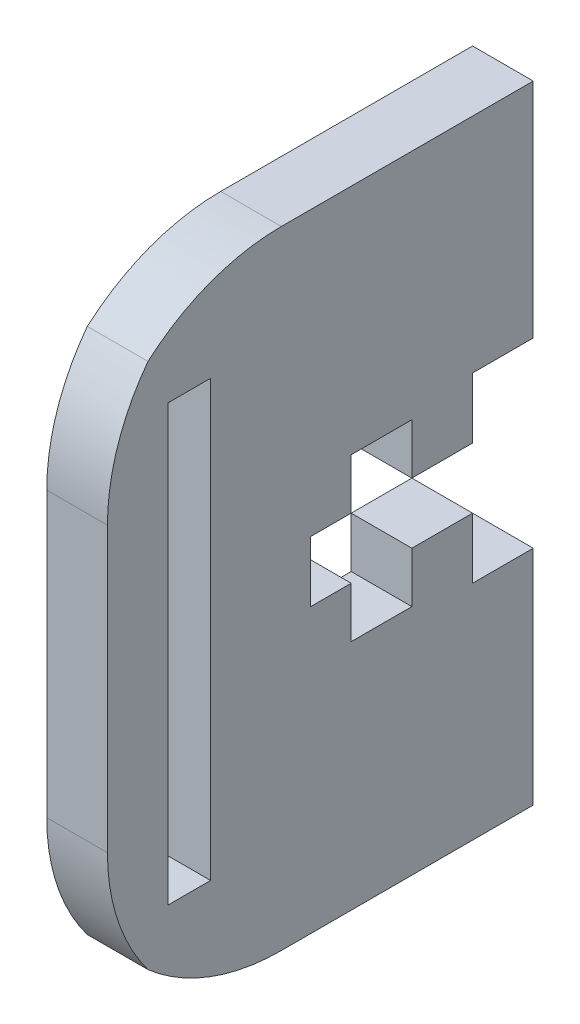
SolidWorks part; units mm, degrees
ref_plane "Alzado" through (0, 0, 0) normal (0, 0, 1) x (1, 0, 0)
ref_plane "Planta" through (0, 0, 0) normal (0, 1, 0) x (1, 0, 0)
ref_plane "Vista lateral" through (0, 0, 0) normal (1, 0, 0) x (0, 0, -1)
sketch "Croquis1" plane through (0, 0, 0) normal (1, 0, 0) x (0, 0, -1)
  line L1 (-10, -12.5) -> (14, -12.5)
  line L2 (-10, -12.5) -> (-10, 12.5)
  line L3 (-10, 12.5) -> (17, 12.5)
  line L5 (-10, -12.5) -> (14, 17.5) construction
  line L6 (-10, 12.5) -> (14, -17.5) construction
  line L8 (14, 4.5) -> (17, 4.5)
  line L10 (14, -4.5) -> (17, -4.5)
  line L12 (14, -4.5) -> (14, 4.5)
  line L13 (-1.05, -10.75) -> (1.05, -10.75)
  line L14 (-1.05, -10.75) -> (-1.05, 10.75)
  line L15 (-1.05, 10.75) -> (1.05, 10.75)
  line L16 (1.05, -10.75) -> (1.05, 10.75)
  line L17 (-1.05, -10.75) -> (1.05, 10.75) construction
  line L18 (-1.05, 10.75) -> (1.05, -10.75) construction
  line L21 (14, 4.5) -> (17, 4.5)
  line L22 (17, 12.5) -> (17, 4.5)
  line L23 (14, -12.5) -> (17, -12.5)
  line L25 (14, -4.5) -> (17, -4.5)
  line L26 (17, -12.5) -> (17, -4.5)
  point P0 (0, 0)
  point P4 (0, 0)
  point P17 (16.9322, 12.5)
  dimension "D1" = 21.5
  dimension "D2" = 25
  dimension "D3" = 2.1
  dimension "D4" = 8
  dimension "D5" = 8
  dimension "D6" = 3
  dimension "D8" = 10
extrude "Saliente-Extruir1" add sketch "Croquis1" along normal mid plane 3 contours L23 L26 L10 L12 L8 L22 L3 L2 L1 L16 L13 L14 L15 region at (0, 0, -3.2247)
fillet "Redondeo1" radius 10 2 edges at (0, -12.5, 10) (0, 12.5, 10)
sketch "Croquis2" plane through (0, 12.5, 0) normal (0, 1, 0) x (1, 0, 0)
  line L4 (-1.5, 17) -> (-1.5, 0)
  line L5 (-1.5, 0) -> (1.5, 0)
  line L6 (-1.5, 17) -> (-1.5, 0)
  line L7 (1.5, 0) -> (1.5, 17)
  line L9 (-1.5, 0) -> (1.5, 0)
  line L12 (1.5, 0) -> (1.5, 17)
  line L13 (1.5, 17) -> (-1.5, 17)
  line L14 (1.5, 17) -> (-1.5, 17)
  dimension "D1" = 0
extrude "Saliente-Extruir2" add sketch "Croquis2" along normal blind 3
sketch "Croquis3" plane through (0, -12.5, 0) normal (0, -1, 0) x (1, 0, 0)
  line L4 (1.5, -17) -> (1.5, 0)
  line L5 (1.5, 0) -> (-1.5, 0)
  line L6 (1.5, -17) -> (1.5, 0)
  line L7 (-1.5, 0) -> (-1.5, -17)
  line L9 (1.5, 0) -> (-1.5, 0)
  line L12 (-1.5, 0) -> (-1.5, -17)
  line L13 (-1.5, -17) -> (1.5, -17)
  line L14 (-1.5, -17) -> (1.5, -17)
  dimension "D1" = 0
extrude "Saliente-Extruir3" add sketch "Croquis3" along normal blind 3
sketch "Croquis4" plane through (-1.5, 0, 0) normal (-1, 0, 0) x (0, 0, 1)
  line L0 (-12, 0) -> (-10.5, 0) construction
  line L1 (-12, 11) -> (-12, -11) construction
  line L2 (-10.5, 11) -> (-10.5, -11) construction
  line L4 (-12.1, -12.4514) -> (-10.4, -12.4514)
  line L5 (-12.1, -12.4514) -> (-12.1, 12.4514)
  line L6 (-12.1, 12.4514) -> (-10.4, 12.4514)
  line L7 (-10.4, -12.4514) -> (-10.4, 12.4514)
  line L8 (-12.1, -12.4514) -> (-10.4, 12.4514) construction
  line L9 (-12.1, 12.4514) -> (-10.4, -12.4514) construction
  point P6 (-11.25, 0)
  dimension "D1" = 0.1
fillet "Redondeo2" radius 10 2 edges at (0, -12.5, 0) (0, 12.5, 0)
fillet "Redondeo3" radius 10 2 edges at (0, -15.5, 0) (0, 15.5, 0)
sketch "Croquis5" plane through (1.5, 0, 0) normal (1, 0, 0) x (0, 0, -1)
  line L0 (-1.05, 10.75) -> (-1.05, -10.75) construction
  line L1 (-25.4979, 18.2535) -> (-4.05, 18.2535)
  line L2 (-25.4979, 18.2535) -> (-25.4979, -19.9876)
  line L3 (-25.4979, -19.9876) -> (-4.05, -19.9876)
  line L4 (-4.05, 18.2535) -> (-4.05, -19.9876)
  dimension "D1" = 3
extrude "Cortar-Extruir2" cut sketch "Croquis5" against normal blind 10
fillet "Redondeo4" radius 10 2 edges at (0, 11.653, 4.05) (0, -11.653, 4.05)
sketch "Croquis6" plane through (1.5, 0, 0) normal (1, 0, 0) x (0, 0, -1)
  line L0 (14, 0) -> (5.8693, 0) construction
  line L1 (14, -4.5) -> (14, 4.5) construction
  line L2 (14, 1.5) -> (11, 1.5)
  line L3 (11, 1.5) -> (11, 4)
  line L4 (11, 4) -> (8, 4)
  line L5 (8, 4) -> (8, 1.5)
  line L6 (8, 1.5) -> (6, 1.5)
  line L7 (6, 1.5) -> (6, -1.5)
  line L8 (14, -1.5) -> (14, 1.5)
  line L9 (8, -1.5) -> (6, -1.5)
  line L10 (8, -4) -> (8, -1.5)
  line L11 (11, -4) -> (8, -4)
  line L12 (11, -1.5) -> (11, -4)
  line L13 (14, -1.5) -> (11, -1.5)
  point P18 (6, 0)
  dimension "D1" = 3
  dimension "D2" = 1.5
  dimension "D3" = 1.5
  dimension "D4" = 0
  dimension "D5" = 8
  dimension "D6" = 2
  dimension "D7" = 2.5
extrude "Cortar-Extruir3" cut sketch "Croquis6" against normal blind 10
